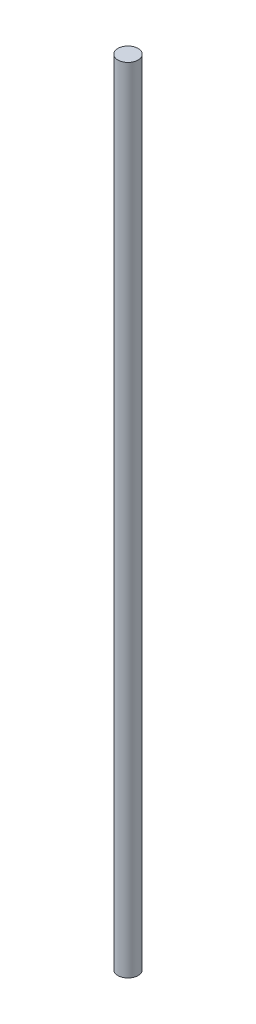
SolidWorks part; units mm, degrees
ref_plane "Front Plane" through (0, 0, 0) normal (0, 0, 1) x (1, 0, 0)
ref_plane "Top Plane" through (0, 0, 0) normal (0, 1, 0) x (1, 0, 0)
ref_plane "Right Plane" through (0, 0, 0) normal (1, 0, 0) x (0, 0, -1)
sketch "Sketch1" plane through (0, 0, 0) normal (0, 1, 0) x (1, 0, 0)
  circle A0 centre (0, 0) radius 3.175
  dimension "D1" = 6.35
extrude "Boss-Extrude1" add sketch "Sketch1" along normal blind 250
